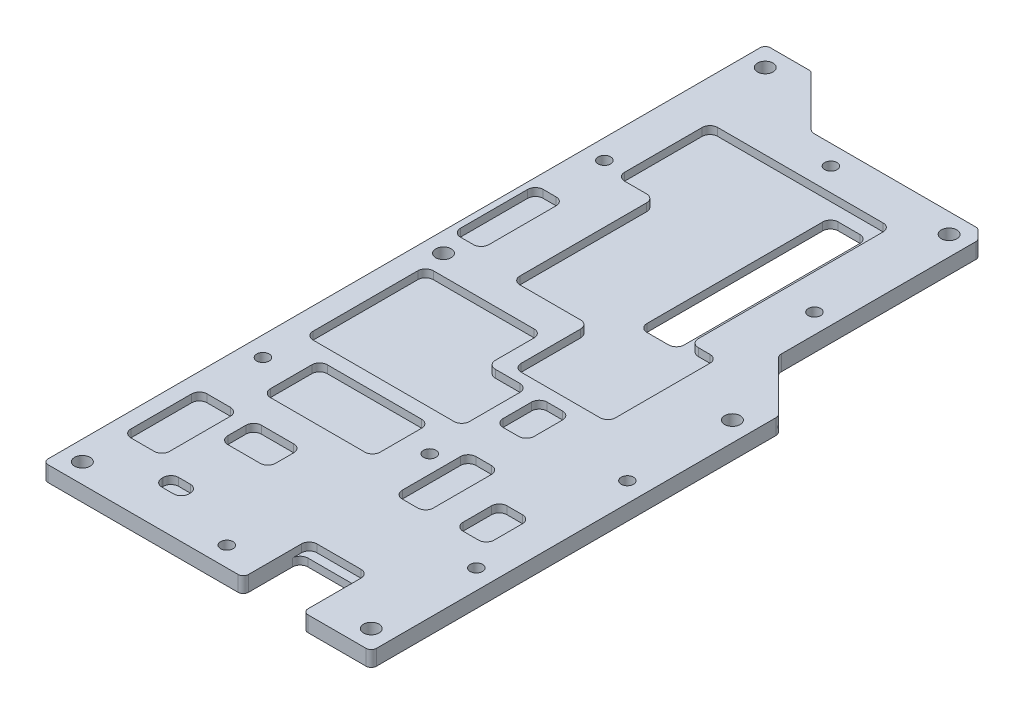
SolidWorks part; units mm, degrees
ref_plane "Front Plane" through (0, 0, 0) normal (0, 0, 1) x (1, 0, 0)
ref_plane "Top Plane" through (0, 0, 0) normal (0, 1, 0) x (1, 0, 0)
ref_plane "Right Plane" through (0, 0, 0) normal (1, 0, 0) x (0, 0, -1)
sketch "Sketch1" plane through (0, 0, 0) normal (0, 1, 0) x (1, 0, 0)
  line L0 (0, 1) -> (0, 138.7)
  line L1 (1, 0) -> (37.75, 0)
  line L2 (63.5, 1) -> (63.5, 78.3258)
  line L3 (1, 139.7) -> (8.4758, 139.7)
  line L4 (19.6713, 129.54) -> (50.8958, 129.54)
  line L5 (9.1829, 139.4071) -> (18.6107, 129.9793)
  line L6 (53.34, 89.5213) -> (53.34, 127.0958)
  line L7 (63.2071, 79.0329) -> (53.7793, 88.4607)
  line L8 (51.6029, 129.2471) -> (53.0471, 127.8029)
  line L13 (38.75, 1) -> (38.75, 9.5)
  line L14 (40.25, 11) -> (48.75, 11)
  line L15 (50.25, 9.5) -> (50.25, 1)
  line L16 (51.25, 0) -> (62.5, 0)
  arc A2 (1, 0) -> (0, 1) centre (1, 1) cw
  arc A3 (63.5, 1) -> (62.5, 0) centre (62.5, 1) cw
  arc A4 (53.7793, 88.4607) -> (53.34, 89.5213) centre (54.84, 89.5213) cw
  arc A5 (18.6107, 129.9793) -> (19.6713, 129.54) centre (19.6713, 131.04) ccw
  arc A6 (63.5, 78.3258) -> (63.2071, 79.0329) centre (62.5, 78.3258) ccw
  arc A7 (53.34, 127.0958) -> (53.0471, 127.8029) centre (52.34, 127.0958) ccw
  arc A8 (51.6029, 129.2471) -> (50.8958, 129.54) centre (50.8958, 128.54) ccw
  arc A9 (9.1829, 139.4071) -> (8.4758, 139.7) centre (8.4758, 138.7) ccw
  arc A10 (1, 139.7) -> (0, 138.7) centre (1, 138.7) ccw
  arc A13 (48.75, 11) -> (50.25, 9.5) centre (48.75, 9.5) cw
  arc A14 (38.75, 9.5) -> (40.25, 11) centre (40.25, 9.5) cw
  arc A15 (50.25, 1) -> (51.25, 0) centre (51.25, 1) ccw
  arc A16 (38.75, 1) -> (37.75, 0) centre (37.75, 1) cw
  point P20 (0, 0)
  point P23 (63.5, 0)
  point P26 (53.34, 88.9)
  point P29 (19.05, 129.54)
  point P32 (63.5, 78.74)
  point P35 (53.34, 127.51)
  point P38 (51.31, 129.54)
  point P41 (8.89, 139.7)
  point P44 (0, 139.7)
  point P45 (38.75, 11)
  point P48 (50.25, 0)
  point P51 (38.75, 0)
  dimension "D14" = 1.5
  dimension "D15" = 1
  dimension "D16" = 1
  dimension "D17" = 1.5
  dimension "D18" = 1
  dimension "D19" = 1
  dimension "D1" = 139.7
  dimension "D2" = 63.5
  dimension "D3" = 78.74
  dimension "D4" = 8.89
  dimension "D5" = 10.16
  dimension "D6" = 10.16
  dimension "D7" = 32.26
  dimension "D8" = 10.16
  dimension "D9" = 10.16
  dimension "D10" = 2.03
  dimension "D11" = 13.25
  dimension "D12" = 11.5
  dimension "D13" = 11
extrude "Boss-Extrude1" add sketch "Sketch1" along normal blind 3
sketch "Sketch2" plane through (0, 3, 0) normal (0, 1, 0) x (1, 0, 0)
  line L36 (50.25, 0) -> (50.25, 11.25)
  line L37 (51.25, 0) -> (62.5, 0) construction
  line L38 (48.75, 12.75) -> (40.25, 12.75)
  line L39 (38.75, 11.25) -> (38.75, 0)
  line L40 (1, 0) -> (37.75, 0) construction
  line L41 (38.75, 0) -> (50.25, 0)
  line L42 (63.5, 1) -> (63.5, 78.3258) construction
  line L43 (0, 138.7) -> (0, 1) construction
  line L44 (52.25, 37.5) -> (55.25, 37.5)
  line L45 (50.75, 36) -> (50.75, 30.5)
  line L46 (52.25, 29) -> (55.25, 29)
  line L47 (56.75, 36) -> (56.75, 30.5)
  line L48 (41, 42.75) -> (44, 42.75)
  line L49 (39.5, 41.25) -> (39.5, 30)
  line L50 (41, 28.5) -> (44, 28.5)
  line L51 (45.5, 41.25) -> (45.5, 30)
  line L52 (11.25, 43.75) -> (29.5, 43.75)
  line L53 (9.75, 42.25) -> (9.75, 34.25)
  line L54 (11.25, 32.75) -> (29.5, 32.75)
  line L55 (31, 42.25) -> (31, 34.25)
  line L56 (18, 10.5) -> (15.75, 10.5)
  line L57 (19.5, 9) -> (19.5, 8.75)
  line L58 (18, 7.25) -> (15.75, 7.25)
  line L59 (14.25, 9) -> (14.25, 8.75)
  line L60 (4.25, 68.25) -> (4.25, 48)
  line L61 (4.5, 27.25) -> (9, 27.25)
  line L62 (3, 25.75) -> (3, 14)
  line L63 (4.5, 12.5) -> (9, 12.5)
  line L64 (10.5, 25.75) -> (10.5, 14)
  line L65 (15, 27.25) -> (21.25, 27.25)
  line L66 (13.5, 25.75) -> (13.5, 22.25)
  line L67 (15, 20.75) -> (21.25, 20.75)
  line L68 (22.75, 25.75) -> (22.75, 22.25)
  line L69 (5.75, 46.5) -> (33, 46.5)
  line L70 (34.5, 48) -> (34.5, 57.75)
  line L71 (33, 59.25) -> (28.25, 59.25)
  line L72 (26.75, 60.75) -> (26.75, 68.25)
  line L73 (25.25, 69.75) -> (5.75, 69.75)
  line L74 (31.25, 61.25) -> (46.5, 61.25)
  line L75 (38.75, 58.75) -> (41.75, 58.75)
  line L76 (37.25, 57.25) -> (37.25, 51.75)
  line L77 (38.75, 50.25) -> (41.75, 50.25)
  line L78 (43.25, 57.25) -> (43.25, 51.75)
  line L79 (48, 62.75) -> (48, 81)
  line L80 (46.5, 82.5) -> (44.25, 82.5)
  line L81 (42.75, 84) -> (42.75, 119.75)
  line L82 (41.25, 121.25) -> (9.25, 121.25)
  line L83 (7.75, 119.75) -> (7.75, 104.75)
  line L84 (9.25, 103.25) -> (13.5, 103.25)
  line L85 (15, 101.75) -> (15, 77.25)
  line L86 (16.5, 75.75) -> (28.25, 75.75)
  line L87 (29.75, 74.25) -> (29.75, 62.75)
  line L89 (2.75, 94) -> (5.25, 94)
  line L90 (1.25, 92.5) -> (1.25, 79.5)
  line L91 (2.75, 78) -> (5.25, 78)
  line L92 (6.75, 92.5) -> (6.75, 79.5)
  arc A32 (50.25, 11.25) -> (48.75, 12.75) centre (48.75, 11.25) ccw
  arc A33 (40.25, 12.75) -> (38.75, 11.25) centre (40.25, 11.25) ccw
  arc A34 (50.75, 30.5) -> (52.25, 29) centre (52.25, 30.5) ccw
  arc A35 (55.25, 29) -> (56.75, 30.5) centre (55.25, 30.5) ccw
  arc A36 (56.75, 36) -> (55.25, 37.5) centre (55.25, 36) ccw
  arc A37 (50.75, 36) -> (52.25, 37.5) centre (52.25, 36) cw
  arc A38 (39.5, 30) -> (41, 28.5) centre (41, 30) ccw
  arc A39 (44, 28.5) -> (45.5, 30) centre (44, 30) ccw
  arc A40 (44, 42.75) -> (45.5, 41.25) centre (44, 41.25) cw
  arc A41 (41, 42.75) -> (39.5, 41.25) centre (41, 41.25) ccw
  arc A42 (29.5, 43.75) -> (31, 42.25) centre (29.5, 42.25) cw
  arc A43 (29.5, 32.75) -> (31, 34.25) centre (29.5, 34.25) ccw
  arc A44 (9.75, 34.25) -> (11.25, 32.75) centre (11.25, 34.25) ccw
  arc A45 (11.25, 43.75) -> (9.75, 42.25) centre (11.25, 42.25) ccw
  arc A46 (19.5, 8.75) -> (18, 7.25) centre (18, 8.75) cw
  arc A47 (18, 10.5) -> (19.5, 9) centre (18, 9) cw
  arc A48 (15.75, 7.25) -> (14.25, 8.75) centre (15.75, 8.75) cw
  arc A49 (15.75, 10.5) -> (14.25, 9) centre (15.75, 9) ccw
  arc A50 (21.25, 20.75) -> (22.75, 22.25) centre (21.25, 22.25) ccw
  arc A51 (21.25, 27.25) -> (22.75, 25.75) centre (21.25, 25.75) cw
  arc A52 (15, 27.25) -> (13.5, 25.75) centre (15, 25.75) ccw
  arc A53 (13.5, 22.25) -> (15, 20.75) centre (15, 22.25) ccw
  arc A54 (3, 14) -> (4.5, 12.5) centre (4.5, 14) ccw
  arc A55 (9, 12.5) -> (10.5, 14) centre (9, 14) ccw
  arc A56 (9, 27.25) -> (10.5, 25.75) centre (9, 25.75) cw
  arc A57 (4.5, 27.25) -> (3, 25.75) centre (4.5, 25.75) ccw
  arc A58 (26.75, 68.25) -> (25.25, 69.75) centre (25.25, 68.25) ccw
  arc A59 (34.5, 57.75) -> (33, 59.25) centre (33, 57.75) ccw
  arc A60 (33, 46.5) -> (34.5, 48) centre (33, 48) ccw
  arc A61 (4.25, 48) -> (5.75, 46.5) centre (5.75, 48) ccw
  arc A62 (5.75, 69.75) -> (4.25, 68.25) centre (5.75, 68.25) ccw
  arc A63 (28.25, 59.25) -> (26.75, 60.75) centre (28.25, 60.75) cw
  arc A64 (41.75, 58.75) -> (43.25, 57.25) centre (41.75, 57.25) cw
  arc A65 (41.75, 50.25) -> (43.25, 51.75) centre (41.75, 51.75) ccw
  arc A66 (37.25, 51.75) -> (38.75, 50.25) centre (38.75, 51.75) ccw
  arc A67 (38.75, 58.75) -> (37.25, 57.25) centre (38.75, 57.25) ccw
  arc A68 (42.75, 119.75) -> (41.25, 121.25) centre (41.25, 119.75) ccw
  arc A69 (44.25, 82.5) -> (42.75, 84) centre (44.25, 84) cw
  arc A70 (48, 81) -> (46.5, 82.5) centre (46.5, 81) ccw
  arc A71 (46.5, 61.25) -> (48, 62.75) centre (46.5, 62.75) ccw
  arc A72 (31.25, 61.25) -> (29.75, 62.75) centre (31.25, 62.75) cw
  arc A73 (28.25, 75.75) -> (29.75, 74.25) centre (28.25, 74.25) cw
  arc A74 (15, 77.25) -> (16.5, 75.75) centre (16.5, 77.25) ccw
  arc A75 (13.5, 103.25) -> (15, 101.75) centre (13.5, 101.75) cw
  arc A76 (7.75, 104.75) -> (9.25, 103.25) centre (9.25, 104.75) ccw
  arc A77 (9.25, 121.25) -> (7.75, 119.75) centre (9.25, 119.75) ccw
  arc A78 (1.25, 79.5) -> (2.75, 78) centre (2.75, 79.5) ccw
  arc A79 (5.25, 78) -> (6.75, 79.5) centre (5.25, 79.5) ccw
  arc A80 (5.25, 94) -> (6.75, 92.5) centre (5.25, 92.5) cw
  arc A81 (2.75, 94) -> (1.25, 92.5) centre (2.75, 92.5) ccw
  point P12 (50.25, 12.75)
  point P15 (38.75, 12.75)
  point P22 (50.75, 29)
  point P25 (56.75, 29)
  point P28 (56.75, 37.5)
  point P37 (39.5, 28.5)
  point P40 (45.5, 28.5)
  point P43 (45.5, 42.75)
  point P56 (31, 32.75)
  point P59 (9.75, 32.75)
  point P62 (9.75, 43.75)
  point P69 (19.5, 7.25)
  point P72 (19.5, 10.5)
  point P77 (14.25, 10.5)
  point P90 (22.75, 27.25)
  point P93 (13.5, 27.25)
  point P96 (13.5, 20.75)
  point P99 (3, 12.5)
  point P104 (10.5, 27.25)
  point P107 (3, 27.25)
  point P117 (26.75, 69.75)
  point P120 (34.5, 59.25)
  point P123 (34.5, 46.5)
  point P126 (4.25, 46.5)
  point P129 (4.25, 69.75)
  point P137 (43.25, 58.75)
  point P142 (37.25, 50.25)
  point P145 (37.25, 58.75)
  point P158 (42.75, 121.25)
  point P161 (42.75, 82.5)
  point P164 (48, 82.5)
  point P167 (48, 61.25)
  point P170 (29.75, 61.25)
  point P175 (15, 75.75)
  point P178 (15, 103.25)
  point P181 (7.75, 103.25)
  point P184 (7.75, 121.25)
  point P192 (1.25, 78)
  point P197 (6.75, 94)
  point P200 (1.25, 94)
  dimension "D35" = 30.25
  dimension "D36" = 12.75
  dimension "D37" = 22.5
  dimension "D38" = 4.25
  dimension "D39" = 46.5
  dimension "D40" = 1.5
  dimension "D41" = 1.5
  dimension "D42" = 8.5
  dimension "D4" = 1.5
  dimension "D9" = 1.5
  dimension "D14" = 1.5
  dimension "D19" = 1.5
  dimension "D24" = 1.5
  dimension "D33" = 1.5
  dimension "D46" = 1.5
  dimension "D57" = 1.5
  dimension "D62" = 1.5
  dimension "D1" = 13.25
  dimension "D2" = 12.75
  dimension "D3" = 11.5
  dimension "D5" = 6
  dimension "D6" = 8.5
  dimension "D7" = 6.75
  dimension "D8" = 29
  dimension "D10" = 14.25
  dimension "D11" = 6
  dimension "D12" = 18
  dimension "D13" = 28.5
  dimension "D15" = 21.25
  dimension "D16" = 11
  dimension "D17" = 32.75
  dimension "D18" = 9.75
  dimension "D20" = 3.25
  dimension "D21" = 5.25
  dimension "D22" = 7.25
  dimension "D23" = 14.25
  dimension "D25" = 14.75
  dimension "D26" = 7.5
  dimension "D27" = 12.5
  dimension "D28" = 3
  dimension "D29" = 6.5
  dimension "D30" = 9.25
  dimension "D31" = 13.5
  dimension "D32" = 20.75
  dimension "D34" = 23.25
  dimension "D43" = 6
  dimension "D44" = 20.25
  dimension "D45" = 50.25
  dimension "D47" = 18.25
  dimension "D48" = 21.25
  dimension "D49" = 5.25
  dimension "D50" = 38.75
  dimension "D51" = 35
  dimension "D52" = 18
  dimension "D53" = 7.25
  dimension "D54" = 27.5
  dimension "D55" = 15.5
  dimension "D56" = 61.25
  dimension "D58" = 16
  dimension "D59" = 5.5
  dimension "D60" = 1.25
  dimension "D61" = 78
extrude "Cut-Extrude1" cut sketch "Sketch2" against normal blind 1.5
sketch "Sketch3" plane through (0, 0, 0) normal (0, -1, 0) x (-1, 0, 0)
  line L0 (-37.34, 118.58) -> (-37.34, 81.58) construction
  line L1 (-39.44, 118.58) -> (-35.24, 118.58)
  line L2 (-40.94, 117.08) -> (-40.94, 83.08)
  line L3 (-39.44, 81.58) -> (-35.24, 81.58)
  line L4 (-33.74, 117.08) -> (-33.74, 83.08)
  line L5 (-40.94, 100.08) -> (-33.74, 100.08) construction
  arc A0 (-40.94, 83.08) -> (-39.44, 81.58) centre (-39.44, 83.08) ccw
  arc A1 (-35.24, 81.58) -> (-33.74, 83.08) centre (-35.24, 83.08) ccw
  arc A2 (-35.24, 118.58) -> (-33.74, 117.08) centre (-35.24, 117.08) cw
  arc A3 (-39.44, 118.58) -> (-40.94, 117.08) centre (-39.44, 117.08) ccw
  point P12 (-40.94, 81.58)
  point P17 (-33.74, 118.58)
  point P20 (-40.94, 118.58)
  dimension "D5" = 1.5
  dimension "D1" = 37
  dimension "D2" = 7.2
  dimension "D3" = 37.34
  dimension "D4" = 100.08
extrude "Cut-Extrude2" cut sketch "Sketch3" against normal up to next
hole_wizard "Ø3.0mm Dowel Hole1" positions "Sketch5" profile "Sketch6" hole size "Ø3.0" standard "ISO" end condition through all
sketch "Sketch5" plane through (0, 3, 0) normal (0, 1, 0) x (1, 0, 0)
  line L0 (51.25, 0) -> (62.5, 0) construction
  line L1 (63.5, 1) -> (63.5, 78.3258) construction
  line L2 (53.34, 89.5213) -> (53.34, 127.0958) construction
  line L3 (50.8958, 129.54) -> (19.6713, 129.54) construction
  line L4 (0, 138.7) -> (0, 1) construction
  line L5 (8.4758, 139.7) -> (1, 139.7) construction
  line L6 (1, 0) -> (37.75, 0) construction
  point P0 (3.81, 135.89)
  point P2 (49.53, 125.73)
  point P4 (59.69, 73.66)
  point P6 (59.69, 3.81)
  point P8 (3.81, 3.81)
  point P10 (3.81, 73.66)
  dimension "D1" = 3.81
  dimension "D2" = 3.81
  dimension "D3" = 3.81
  dimension "D4" = 3.81
  dimension "D5" = 3.81
  dimension "D6" = 3.81
  dimension "D7" = 3.81
  dimension "D8" = 3.81
  dimension "D9" = 3.81
  dimension "D10" = 3.81
  dimension "D11" = 69.85
  dimension "D12" = 69.85
sketch "Sketch6" plane through (3.81, 3, -135.89) normal (1, 0, 0) x (0, 0, 1)
  line L0 (0, 0) -> (0, 3)
  line L1 (0, 3) -> (1.5, 3)
  line L2 (1.5, 3) -> (1.5, 0)
  line L5 (1.5, 0) -> (0, 0)
  line L11 (0, -6.35) -> (0, 107.95) construction
  dimension "Thru Hole Dia." = 3
  dimension "Thru Hole Depth" = 3
hole_wizard "CSK for M2 Countersunk Raised Head Screw1" positions "Sketch7" profile "Sketch8" countersink size "M2" standard "ISO" end condition through all
sketch "Sketch7" plane through (0, 0, 0) normal (0, -1, 0) x (-1, 0, 0)
  line L0 (0, 138.7) -> (0, 1) construction
  line L1 (-50.8958, 129.54) -> (-19.6713, 129.54) construction
  line L2 (-1, 0) -> (-37.75, 0) construction
  line L3 (-63.5, 1) -> (-63.5, 78.3258) construction
  line L4 (-53.34, 89.5213) -> (-53.34, 127.0958) construction
  circle A0 centre (-59.69, 3.81) radius 1.5 construction
  circle A2 centre (-3.81, 3.81) radius 1.5 construction
  circle A3 centre (-3.81, 135.89) radius 1.5 construction
  circle A4 centre (-49.53, 125.73) radius 1.5 construction
  point P0 (-26.67, 125.73)
  point P2 (-31.75, 3.81)
  point P4 (-59.69, 53.34)
  point P6 (-3.81, 38.74)
  point P8 (-36.07, 38.74)
  point P10 (-59.69, 24.13)
  point P12 (-49.53, 99.69)
  point P14 (-3.81, 104.77)
  dimension "D1" = 3.81
  dimension "D2" = 3.81
  dimension "D3" = 3.81
  dimension "D4" = 3.81
  dimension "D5" = 3.81
  dimension "D6" = 3.81
  dimension "D7" = 3.81
  dimension "D8" = 49.53
  dimension "D9" = 20.32
  dimension "D10" = 32.26
  dimension "D11" = 27.94
  dimension "D12" = 34.93
  dimension "D13" = 31.12
  dimension "D14" = 26.04
  dimension "D15" = 22.86
sketch "Sketch8" plane through (26.67, 0, -125.73) normal (1, 0, 0) x (0, 0, -1)
  line L0 (0, 0) -> (0, 3)
  line L1 (0, 3) -> (1.2, 3)
  line L2 (1.2, 3) -> (1.2, 1)
  line L3 (1.2, 1) -> (2.2, 0)
  line L5 (2.2, 0) -> (0, 0)
  line L6 (-1.2, 1) -> (-2.2, 0) construction
  line L11 (0, -6.35) -> (0, 107.95) construction
  dimension "Thru Hole Dia." = 2.4
  dimension "Thru Hole Depth" = 3
  dimension "Near C'Sink Dia." = 4.4
  dimension "Near C'Sink Angle" = 90
